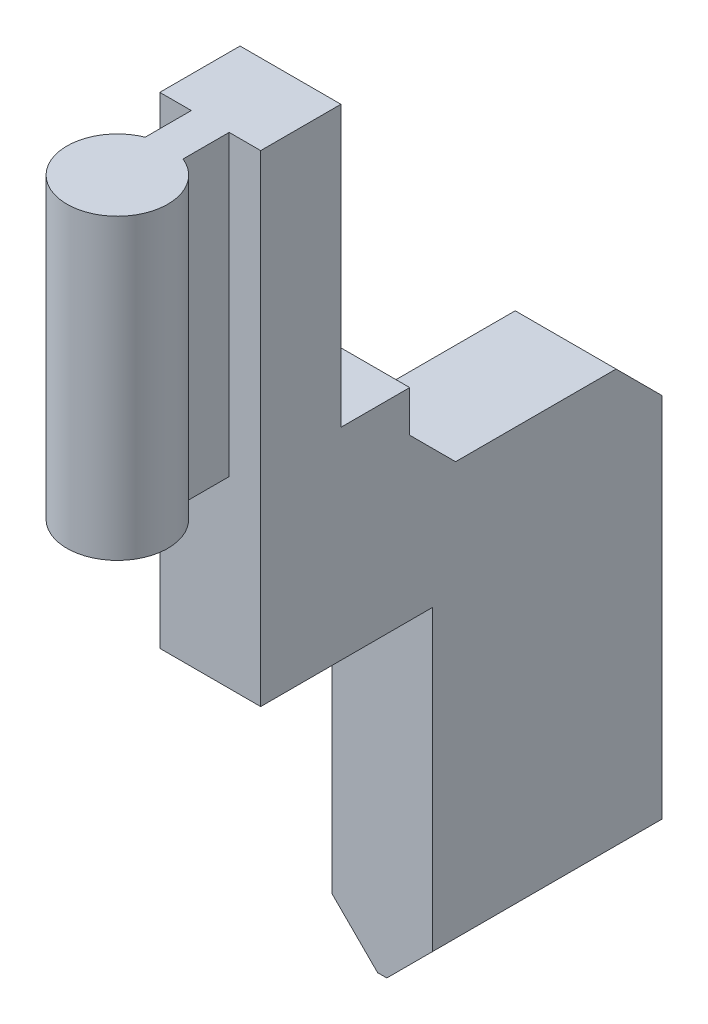
SolidWorks part; units mm, degrees
ref_plane "Płaszczyzna przednia" through (0, 0, 0) normal (0, 0, 1) x (1, 0, 0)
ref_plane "Płaszczyzna górna" through (0, 0, 0) normal (0, 1, 0) x (1, 0, 0)
ref_plane "Płaszczyzna prawa" through (0, 0, 0) normal (1, 0, 0) x (0, 0, -1)
sketch "Szkic1" plane through (0, 0, 0) normal (0, 0, 1) x (1, 0, 0)
  line L1 (-2.2, 10.5) -> (2.2, 10.5)
  line L2 (-2.2, 10.5) -> (-2.2, -10.5)
  line L3 (-2.2, -10.5) -> (2.2, -10.5)
  line L4 (2.2, 10.5) -> (2.2, -10.5)
  line L5 (-2.2, 10.5) -> (2.2, -10.5) construction
  line L6 (-2.2, -10.5) -> (2.2, 10.5) construction
  point P0 (0, 0)
  dimension "D1" = 4.4
  dimension "D2" = 21
extrude "Dodanie-wyciągnięcie1" add sketch "Szkic1" along normal blind 6.5
sketch "Szkic3" plane through (0, 10.5, 0) normal (0, 1, 0) x (1, 0, 0)
  line L0 (0, -6.5) -> (0, -10.55) construction
  line L1 (2.2, -6.5) -> (-2.2, -6.5) construction
  line L3 (0.825, -6.5) -> (0.825, -10.55)
  line L4 (0.825, -6.5) -> (-0.825, -6.5)
  line L5 (-0.825, -6.5) -> (-0.825, -10.55)
  line L6 (0.825, -10.55) -> (-0.825, -10.55)
  line L7 (0.825, -6.5) -> (-0.825, -10.55) construction
  line L8 (-0.825, -6.5) -> (0.825, -10.55) construction
  circle A0 centre (0, -10.55) radius 2.2
  point P5 (0, -8.525)
  point P11 (0, 0)
  line M10 (-2.2, 0) -> (-2.2, -6.5)
  dimension "D2" = 4.4
  dimension "D1" = 4.05
  dimension "D3" = 1.65
extrude "Dodanie-wyciągnięcie2" add sketch "Szkic3" against normal blind 13 contours L5 A0 L3 L6 | L3 A0 L5 L6 | A0 L3 L5 M10 region at (0, 10.5, 7.4519) region at (0, 10.5, 10.8763) region at (0, 10.5, 9.4758)
sketch "Sketch1" plane through (0, 0, 0) normal (0, 0, -1) x (-1, 0, 0)
  line L0 (-2.2, -10.5) -> (-2.2, 10.5) construction
  line L1 (-2.2, -5.5) -> (2.2, -5.5)
  line L2 (-2.2, -5.5) -> (-2.2, -10.5)
  line L3 (-2.2, -10.5) -> (2.2, -10.5)
  line L4 (2.2, -5.5) -> (2.2, -10.5)
  line L5 (0, -10.5) -> (0, -5.5) construction
  line L6 (-2.2, -8) -> (2.2, -8) construction
  line L7 (2.2, 10.5) -> (2.2, -10.5) construction
  line L9 (2.2, -10.5) -> (-2.2, -10.5) construction
  point P460 (0, -8)
  dimension "D1" = 5
extrude "Boss-Extrude1" add sketch "Sketch1" along normal blind 11
sketch "Sketch3" plane through (0, -10.5, 0) normal (0, -1, 0) x (1, 0, 0)
  line L0 (2.2, -11) -> (-2.2, -11) construction
  line L1 (2.2, -11) -> (-2.2, -11)
  line L2 (2.2, -11) -> (2.2, -1)
  line L3 (2.2, -1) -> (-2.2, -1)
  line L4 (-2.2, -11) -> (-2.2, -1)
  line L5 (0, -1) -> (0, -11) construction
  line L6 (2.2, -6) -> (-2.2, -6) construction
  line L7 (2.2, 6.5) -> (2.2, -11) construction
  line L8 (-2.2, 6.5) -> (-2.2, -11) construction
  point P448 (0, -6)
  dimension "D2" = 10
extrude "Boss-Extrude3" add sketch "Sketch3" along normal blind 15
chamfer "Chamfer1" distance 2 angle 45 4 edges at (2.2, -25.5, -6) (-2.2, -25.5, -6) (0, -5.5, 0) (0, -5.5, -11)
sketch "Sketch5" plane through (0, 10.5, 0) normal (0, 1, 0) x (1, 0, 0)
  line L0 (2.2, -6.5) -> (2.2, 0) construction
  line L1 (-2.2, 0) -> (2.2, 0)
  line L2 (-2.2, 0) -> (-2.2, -3)
  line L3 (-2.2, -3) -> (2.2, -3)
  line L4 (2.2, 0) -> (2.2, -3)
  line L5 (0, -3) -> (0, 0) construction
  line L6 (-2.2, -1.5) -> (2.2, -1.5) construction
  point P212 (0, -1.5)
  dimension "D1" = 3
extrude "Cut-Extrude1" cut sketch "Sketch5" against normal blind 12.2
